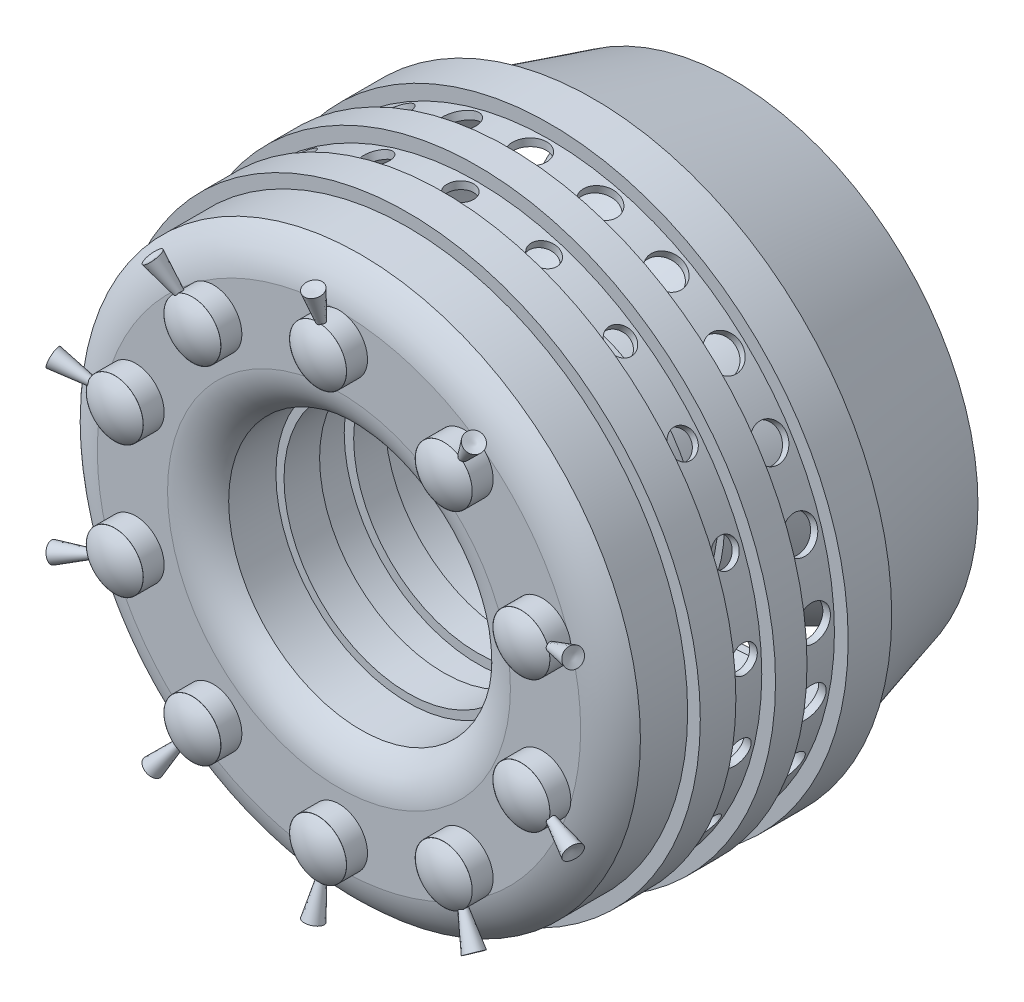
SolidWorks part; units mm, degrees
ref_plane "Front Plane" through (0, 0, 0) normal (0, 0, 1) x (1, 0, 0)
ref_plane "Top Plane" through (0, 0, 0) normal (0, 1, 0) x (1, 0, 0)
ref_plane "Right Plane" through (0, 0, 0) normal (1, 0, 0) x (0, 0, -1)
sketch "Sketch8" plane through (0, 0, 0) normal (1, 0, 0) x (0, 0, -1)
  line L0 (0, 0) -> (5590, 0) construction
  line L1 (0, 0) -> (5607.581, 0)
  line L2 (375.2101, 261.6749) -> (557.709, 261.6749)
  line L3 (557.709, 261.6749) -> (557.709, 0)
  line L4 (557.709, 0) -> (0, 0)
  spline S0 degree 2 poles (0, 0) (27.9707, 205.406) (375.2101, 261.6749) knots 0 0 0 1 1 1
  dimension "D1" = 5590
sketch "Sketch9" plane through (0, 0, 0) normal (1, 0, 0) x (0, 0, -1)
  line L0 (0, 0) -> (5607.581, 0) construction
  line L1 (557.709, 261.6749) -> (557.709, 0) construction
  line L2 (375.2101, 261.6749) -> (557.709, 261.6749) construction
  line L3 (0, 0) -> (5607.581, 0)
  line L4 (557.709, 261.6749) -> (557.709, 0)
  line L5 (375.2101, 261.6749) -> (557.709, 261.6749)
  line L6 (557.709, 0) -> (0, 0)
  parabola Q0 (0, 0) -> (375.2101, 261.6749) focus (120.2694, 20.1897) apex (19.5309, 67.2468) construction
  parabola Q1 (0, 0) -> (375.2101, 261.6749) focus (120.2694, 20.1897) apex (19.5309, 67.2468)
  point P7 (466.4596, 0)
  dimension "D1" = 261.6749
  dimension "D2" = 182.4989
sketch "Sketch11" plane through (0, 0, 0) normal (1, 0, 0) x (0, 0, -1)
  line L0 (557.709, 231.1749) -> (607.709, 231.1749)
  line L1 (557.709, 261.6749) -> (557.709, 0) construction
  line L2 (607.709, 231.1749) -> (607.709, 0)
  line L3 (0, 0) -> (5607.581, 0) construction
  line L5 (375.2101, 261.6749) -> (557.709, 261.6749) construction
  line L7 (607.709, 0) -> (557.709, 0)
  line L8 (557.709, 231.1749) -> (557.709, 0)
  dimension "D2" = 30.5
sketch "Sketch57" plane through (0, 0, 0) normal (1, 0, 0) x (0, 0, -1)
  line L0 (3313.9709, 635.1854) -> (3313.9709, 450.6136)
  line L1 (3370.4201, 735.8678) -> (3494.5647, 735.8678)
  line L2 (3494.5647, 735.8678) -> (3494.5647, 769.0838)
  line L3 (3494.5647, 769.0838) -> (3588.0702, 769.0838)
  line L4 (3677.6097, 747.6177) -> (3588.0702, 747.6177)
  line L5 (3588.0702, 747.6177) -> (3588.0702, 769.0838)
  line L6 (3333.9709, 633.6579) -> (3333.9709, 451.0594)
  line L7 (3377.8416, 367.3644) -> (3515.5307, 367.3644)
  line L8 (3515.5307, 367.3644) -> (3515.5307, 346.0458)
  line L9 (3677.6097, 747.6177) -> (3677.6097, 783.7663)
  line L10 (3677.6097, 783.7663) -> (3760.3558, 783.7663)
  line L11 (3760.3558, 783.7663) -> (3760.3558, 747.6177)
  line L12 (3760.3558, 747.6177) -> (3868.6196, 747.6177)
  line L13 (3868.6196, 747.6177) -> (3868.6196, 783.7663)
  line L14 (3868.6196, 783.7663) -> (3983.0078, 783.7663)
  line L15 (3983.0078, 783.7663) -> (3983.0078, 747.6177)
  line L16 (3371.3907, 347.3644) -> (3495.5307, 347.3644)
  line L17 (3495.5307, 347.3644) -> (3495.5307, 326.0458)
  line L18 (3495.5307, 326.0458) -> (3589.0362, 326.0458)
  line L19 (3589.0362, 326.0458) -> (3589.0362, 350.8344)
  line L20 (3589.0362, 350.8344) -> (3678.5757, 350.8344)
  line L21 (3678.5757, 350.8344) -> (3678.5757, 326.0458)
  line L22 (3678.5757, 326.0458) -> (3761.2572, 326.0458)
  line L23 (3761.2572, 326.0458) -> (3761.2572, 350.8344)
  line L24 (3761.2572, 350.8344) -> (3869.521, 350.8344)
  line L25 (3869.521, 350.8344) -> (3869.521, 326.0458)
  line L26 (3869.521, 326.0458) -> (3983.0078, 326.0458)
  line L27 (3983.0078, 326.0458) -> (3983.0078, 350.8344)
  line L28 (3983.0078, 350.8344) -> (4349.0992, 514.5121)
  line L30 (3515.5307, 346.0458) -> (3569.0362, 346.0458)
  line L31 (3569.0362, 346.0458) -> (3569.0362, 370.8344)
  line L32 (3569.0362, 370.8344) -> (3698.5757, 370.8344)
  line L33 (3698.5757, 370.8344) -> (3698.5757, 346.0458)
  line L34 (3698.5757, 346.0458) -> (3741.2572, 346.0458)
  line L35 (3741.2572, 346.0458) -> (3741.2572, 370.8344)
  line L36 (3741.2572, 370.8344) -> (3889.521, 370.8344)
  line L37 (3889.521, 370.8344) -> (3889.521, 346.0458)
  line L38 (3889.521, 346.0458) -> (3963.0078, 346.0458)
  line L39 (3963.0078, 346.0458) -> (3963.0078, 363.8004)
  line L40 (3963.0078, 363.8004) -> (4329.0992, 527.4781)
  line L42 (3963.0078, 763.7663) -> (3963.0078, 732.4756)
  line L43 (3888.6196, 763.7663) -> (3963.0078, 763.7663)
  line L44 (3888.6196, 727.6177) -> (3888.6196, 763.7663)
  line L45 (3740.3558, 727.6177) -> (3888.6196, 727.6177)
  line L46 (3740.3558, 763.7663) -> (3740.3558, 727.6177)
  line L47 (3697.6097, 763.7663) -> (3740.3558, 763.7663)
  line L48 (3697.6097, 727.6177) -> (3697.6097, 763.7663)
  line L49 (3697.6097, 727.6177) -> (3568.0702, 727.6177)
  line L50 (3568.0702, 727.6177) -> (3568.0702, 749.0838)
  line L51 (3514.5647, 749.0838) -> (3568.0702, 749.0838)
  line L52 (3514.5647, 715.8678) -> (3514.5647, 749.0838)
  line L53 (3377.9522, 715.8678) -> (3514.5647, 715.8678)
  line L54 (4349.0992, 514.5121) -> (4349.0992, 644.4308) construction
  line L55 (4329.0992, 527.4781) -> (4329.0992, 629.2888) construction
  line L56 (4329.0992, 629.2888) -> (4349.0992, 629.2888)
  line L57 (4349.0992, 629.2888) -> (4349.0992, 644.4308)
  line L58 (4329.0992, 527.4781) -> (4349.0992, 527.4781)
  line L59 (4349.0992, 527.4781) -> (4349.0992, 514.5121)
  arc A0 (3313.9709, 635.1854) -> (3370.4201, 735.8678) centre (3474.5696, 611.3089) cw
  arc A1 (3313.9709, 450.6136) -> (3371.3907, 347.3644) centre (3445.6541, 456.2554) ccw
  arc A2 (3333.9709, 451.0594) -> (3377.8416, 367.3644) centre (3445.6541, 456.2554) ccw
  arc A3 (3333.9709, 633.6579) -> (3377.9522, 715.8678) centre (3474.5696, 611.3089) cw
  arc A6 (3313.9709, 450.6136) -> (3371.3907, 347.3644) centre (3445.6541, 456.2554) ccw construction
  arc A7 (3313.9709, 635.1854) -> (3370.4201, 735.8678) centre (3474.5696, 611.3089) cw construction
  spline S0 degree 1 poles (3983.0078, 747.6177) (4349.0992, 644.4308) knots 0 0 1 1
  spline S1 degree 1 poles (3963.0078, 732.4756) (4329.0992, 629.2888) knots 0 0 1 1 construction
  spline S2 degree 1 poles (4329.0992, 629.2888) (3963.0078, 732.4756) knots -0.03981 -0.03981 0.96019 0.96019
  point P64 (3368.2482, 737.675)
  point P68 (3370.4201, 345.7795)
  dimension "D4" = 162.3639
  dimension "D5" = 142.3639
  dimension "D7" = 131.804
  dimension "D8" = 111.804
  dimension "D21" = 380.3557
  dimension "D2" = 124.1446
  dimension "D3" = 124.14
  dimension "D6" = 184.5718
  dimension "D9" = 136.6125
  dimension "D10" = 137.6891
  dimension "D11" = 93.5055
  dimension "D12" = 33.216
  dimension "D13" = 53.5055
  dimension "D14" = 89.5395
  dimension "D15" = 89.5395
  dimension "D16" = 93.5055
  dimension "D17" = 129.5395
  dimension "D18" = 82.7461
  dimension "D19" = 108.2638
  dimension "D20" = 114.3882
  dimension "D22" = 366.0915
  dimension "D23" = 113.4867
  dimension "D24" = 148.2638
  dimension "D25" = 108.2638
  dimension "D26" = 73.4867
  dimension "D1" = 20
revolve "Revolve8" add sketch "Sketch57" angle 360 about L1
sketch "Sketch62" plane through (0, 0, 0) normal (1, 0, 0) x (0, 0, -1)
  line L0 (3313.9709, 591.8369) -> (3268.9709, 591.8369)
  line L1 (3313.9709, 635.1854) -> (3313.9709, -635.1854) construction
  line L2 (3268.9709, 591.8369) -> (3268.9709, 626.8369)
  line L3 (3268.9709, 626.8369) -> (3313.9709, 626.8369)
  line L4 (3313.9709, 626.8369) -> (3313.9709, 591.8369)
  line L5 (3313.9709, 561.8369) -> (3122.8781, 561.8369)
  dimension "D1" = 45
  dimension "D2" = 35
  dimension "D3" = 30
revolve "Revolve-Thin5" add sketch "Sketch62" angle 360 about L5 wall 10
sketch "Sketch64" plane through (0, 0, -3313.9709) normal (0, 0, 1) x (1, 0, 0)
  circle A0 centre (0, 561.8369) radius 20 construction
  circle A1 centre (0, 561.8369) radius 20
  circle M2 centre (0, 561.8369) radius 20
extrude "Cut-Extrude1" cut sketch "Sketch64" against normal blind 50 contours M2 region at (0, 561.8369, -3313.9709)
pattern_circular "CirPattern12" count 10 over 360 about axis through (0, 0, 0) along (0, 0, -1) of "Cut-Extrude1"
ref_plane "Plane27" through (0, 747.6177, 0) normal (0, 1, 0) x (1, 0, 0)
sketch "Sketch66" plane through (0, 747.6177, 0) normal (0, 1, 0) x (1, 0, 0)
  line L0 (-747.6177, 3632.8399) -> (-35, 3632.8399) construction
  line L1 (-747.6177, 3677.6097) -> (-747.6177, 3588.0702) construction
  line L2 (747.6177, 3588.0702) -> (747.6177, 3677.6097) construction
  line L3 (0, 3677.6097) -> (0, 3667.8399) construction
  line L4 (-747.6177, 3677.6097) -> (747.6177, 3677.6097) construction
  line L5 (769.0838, 3588.0702) -> (-769.0838, 3588.0702) construction
  line L6 (0, 3597.8399) -> (0, 3588.0702) construction
  line L7 (35, 3632.8399) -> (747.6177, 3632.8399) construction
  circle A0 centre (0, 3632.8399) radius 35
extrude "Cut-Extrude2" cut sketch "Sketch66" against normal blind 50
pattern_circular "CirPattern13" count 21 over 360 about axis through (0, 0, 0) along (0, 0, -1) of "Cut-Extrude2" reverse direction yes
sketch "Sketch67" plane through (0, 747.6177, 0) normal (0, 1, 0) x (1, 0, 0)
  line L0 (-747.6177, 3814.4877) -> (747.6177, 3814.4877) construction
  line L1 (-747.6177, 3868.6196) -> (-747.6177, 3760.3558) construction
  line L2 (747.6177, 3760.3558) -> (747.6177, 3868.6196) construction
  line L3 (0, 3868.6196) -> (0, 3760.3558) construction
  line L4 (-747.6177, 3868.6196) -> (747.6177, 3868.6196) construction
  line L5 (783.7663, 3760.3558) -> (-783.7663, 3760.3558) construction
  circle A0 centre (0, 3814.4877) radius 45
extrude "Cut-Extrude3" cut sketch "Sketch67" against normal blind 50
pattern_circular "CirPattern14" count 25 over 360 about axis through (0, 0, 0) along (0, 0, -1) of "Cut-Extrude3" reverse direction yes
sketch "Sketch68" plane through (0, 0, 0) normal (1, 0, 0) x (0, 0, -1)
  line L0 (3258.9709, 636.8369) -> (3258.9709, 636.7299)
  line L1 (3258.9709, 561.8369) -> (3231.9106, 561.7834)
  arc A0 (3258.9709, 636.7299) -> (3231.9106, 561.7834) centre (3349.2272, 561.7834) ccw
  spline S0 degree 1 poles (3258.9709, 636.7299) (3258.9709, 561.8369) knots 0 0 1 1
revolve "Revolve12" add sketch "Sketch68" angle 360 about L1
sketch "Sketch69" plane through (0, 0, 0) normal (1, 0, 0) x (0, 0, -1)
  line L0 (3269.7535, 724.0834) -> (3281.3347, 591.8369)
  line L1 (3313.9709, 591.8369) -> (3268.9709, 591.8369) construction
  line L2 (3269.7535, 724.0834) -> (3247.8618, 712.207)
  line L3 (3247.8618, 712.207) -> (3277.8614, 591.8369)
  line L4 (3277.8614, 591.8369) -> (3281.3347, 591.8369)
revolve "Revolve16" add sketch "Sketch69" angle 360 about L3 region at (0, 670.7016, -3266.6441)
pattern_circular "CirPattern11" count 10 over 360 about axis through (0, 0, 0) along (0, 0, -1) of "Revolve-Thin5", "Revolve12", "Revolve16" reverse direction yes
